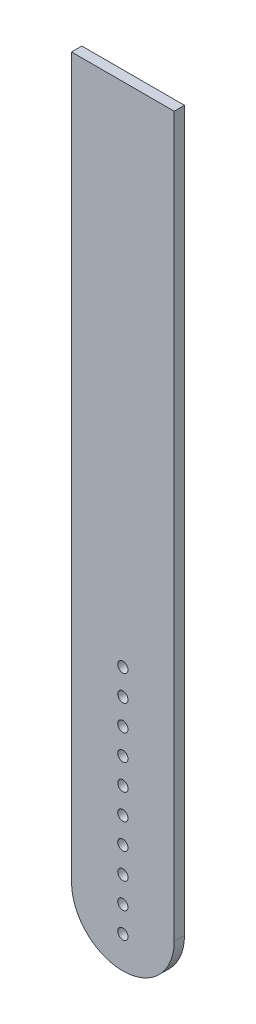
SolidWorks part; units mm, degrees
ref_plane "Front Plane" through (0, 0, 0) normal (0, 0, 1) x (1, 0, 0)
ref_plane "Top Plane" through (0, 0, 0) normal (0, 1, 0) x (1, 0, 0)
ref_plane "Right Plane" through (0, 0, 0) normal (1, 0, 0) x (0, 0, -1)
sketch "Sketch1" plane through (0, 0, 0) normal (0, 1, 0) x (1, 0, 0)
  line L1 (-20, 2) -> (20, 2)
  line L2 (-20, 2) -> (-20, -2)
  line L3 (-20, -2) -> (20, -2)
  line L4 (20, 2) -> (20, -2)
  line L5 (-20, 2) -> (20, -2) construction
  line L6 (-20, -2) -> (20, 2) construction
  point P0 (0, 0)
extrude "Boss-Extrude1" add sketch "Sketch1" along normal blind 300
fillet "Fillet1" radius 20 2 edges at (-20, 0, 0) (20, 0, 0)
sketch "Sketch2" plane through (0, 0, 2) normal (0, 0, 1) x (1, 0, 0)
  circle A0 centre (0, 12.5) radius 2
  dimension "D1" = 12.5
extrude "Cut-Extrude1" cut sketch "Sketch2" against normal through all
pattern_linear "LPattern1" count 10 spacing 10 along (0, 1, 0) of "Cut-Extrude1"
sketch "Sketch6" plane through (0, 0, -2) normal (0, 0, -1) x (-1, 0, 0)
  line L1 (-6.5, 1.0857) -> (-8.5, 1.0857)
  line L2 (-6.5, 1.0857) -> (-6.5, 106.5163)
  line L3 (-6.5, 106.5163) -> (-8.5, 106.5163)
  line L4 (-8.5, 1.0857) -> (-8.5, 106.5163)
  line L5 (-7.5, 106.5163) -> (-7.5, 1.0857) construction
  line L6 (-6.5, 53.801) -> (-8.5, 53.801) construction
  line L7 (-20, 300) -> (-20, 20) construction
  arc A0 (-20, 20) -> (0, 0) centre (0, 20) ccw construction
  point P7 (-7.9927, 1.6665)
  point P524 (-7.5, 53.801)
  dimension "D1" = 2
  dimension "D2" = 12.5
extrude "Cut-Extrude3" cut sketch "Sketch6" against normal blind 2 contours L3 L4 L1 L2
fillet "Fillet2" radius 1 2 edges at (8.5, 106.5163, -1) (6.5, 106.5163, -1)
mirror "Mirror1" about plane through (0, 0, 0) normal (1, 0, 0) of "Fillet2", "Cut-Extrude3"
